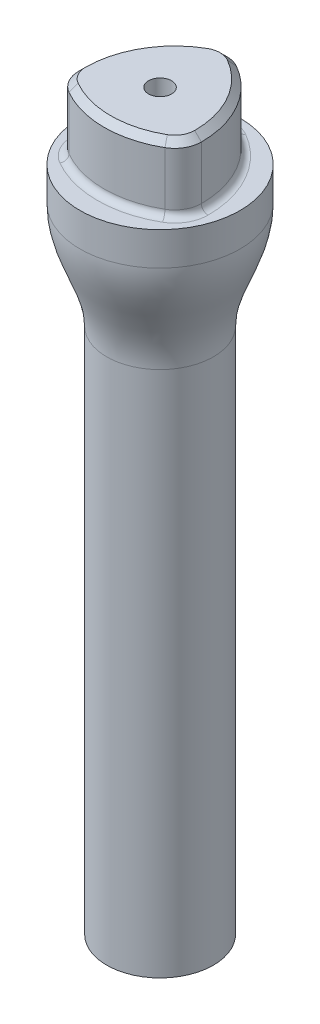
SolidWorks part; units mm, degrees
ref_plane "Front Plane" through (0, 0, 0) normal (0, 0, 1) x (1, 0, 0)
ref_plane "Top Plane" through (0, 0, 0) normal (0, 1, 0) x (1, 0, 0)
ref_plane "Right Plane" through (0, 0, 0) normal (1, 0, 0) x (0, 0, -1)
sketch "Sketch6" plane through (0, 0, 0) normal (0, 0, 1) x (1, 0, 0)
  line L0 (0, 0) -> (-8, 0)
  line L1 (-8, 0) -> (-8, 79)
  line L2 (0, 0) -> (0, 100)
  line L3 (0, 100) -> (-12, 100)
  line L4 (-12, 100) -> (-12, 95)
  line L5 (-12, 95) -> (-12, 89) construction
  line L6 (-12, 89) -> (-8, 85) construction
  line L7 (-8, 85) -> (-8, 79) construction
  spline S0 degree 3 poles (-12, 95) (-12, 89) (-8, 85) (-8, 79) knots 0 0 0 0 1 1 1 1
  point P9 (-10, 33.8018)
  point P10 (-10, 40.4842)
  dimension "D1" = 8
  dimension "D2" = 12
  dimension "D3" = 6
  dimension "D4" = 5
  dimension "D5" = 45
  dimension "D6" = 100
revolve "Revolve1" add sketch "Sketch6" angle 360 about L2
sketch "Sketch7" plane through (0, 100, 0) normal (0, 1, 0) x (1, 0, 0)
  line L1 (0, 6) -> (-5.1962, -3) construction
  line L2 (-5.1962, -3) -> (5.1962, -3) construction
  line L3 (5.1962, -3) -> (0, 6) construction
  circle A0 centre (0, 0) radius 6 construction
  arc A1 (-2, 9.4641) -> (2, 9.4641) centre (0, 6) cw
  arc A2 (9.1962, -3) -> (7.1962, -6.4641) centre (5.1962, -3) cw
  arc A3 (-7.1962, -6.4641) -> (-9.1962, -3) centre (-5.1962, -3) cw
  arc A4 (-9.1962, -3) -> (-2, 9.4641) centre (5.1962, -3) cw
  arc A5 (2, 9.4641) -> (9.1962, -3) centre (-5.1962, -3) cw
  arc A6 (7.1962, -6.4641) -> (-7.1962, -6.4641) centre (0, 6) cw
  circle A8 centre (0, 0) radius 10 construction
  dimension "D1" = 4
  dimension "D2" = 20
extrude "Boss-Extrude2" add sketch "Sketch7" along normal blind 10
sketch "Sketch8" plane through (0, 110, 0) normal (0, 1, 0) x (1, 0, 0)
  point P0 (0, 0)
hole_wizard "#8-32 Tapped Hole2" positions "Sketch8" profile "Sketch9" tap size "#8-32" standard "ANSI Inch"
sketch "Sketch9" plane through (0, 110, 0) normal (1, 0, 0) x (0, 0, 1)
  line L0 (0, 0) -> (0, 13.0378)
  line L1 (0, 13.0378) -> (1.7272, 12)
  line L2 (1.7272, 12) -> (1.7272, 0)
  line L5 (1.7272, 0) -> (0, 0)
  line L10 (0, 13.0378) -> (-1.7272, 12) construction
  line L11 (0, -6.35) -> (0, 107.95) construction
  dimension "Tap Drill Dia." = 3.4544
  dimension "Tap Drill Depth" = 12
  dimension "Drill Angle" = 118
cosmetic thread "Hole Thread2" parameters "D1"=8.33, "D2"=4.1656
fillet "Fillet1" radius 1 6 edges at (0, 100, -10) (7.2679, 100, -4.1962) (8.6603, 100, 5) (0, 100, 8.3923) (-8.6603, 100, 5) (-7.2679, 100, -4.1962)
chamfer "Chamfer1" distance 1 angle 45 6 edges at (8.6603, 110, 5) (7.2679, 110, -4.1962) (0, 110, 8.3923) (0, 110, -10) (-8.6603, 110, 5) (-7.2679, 110, -4.1962)
